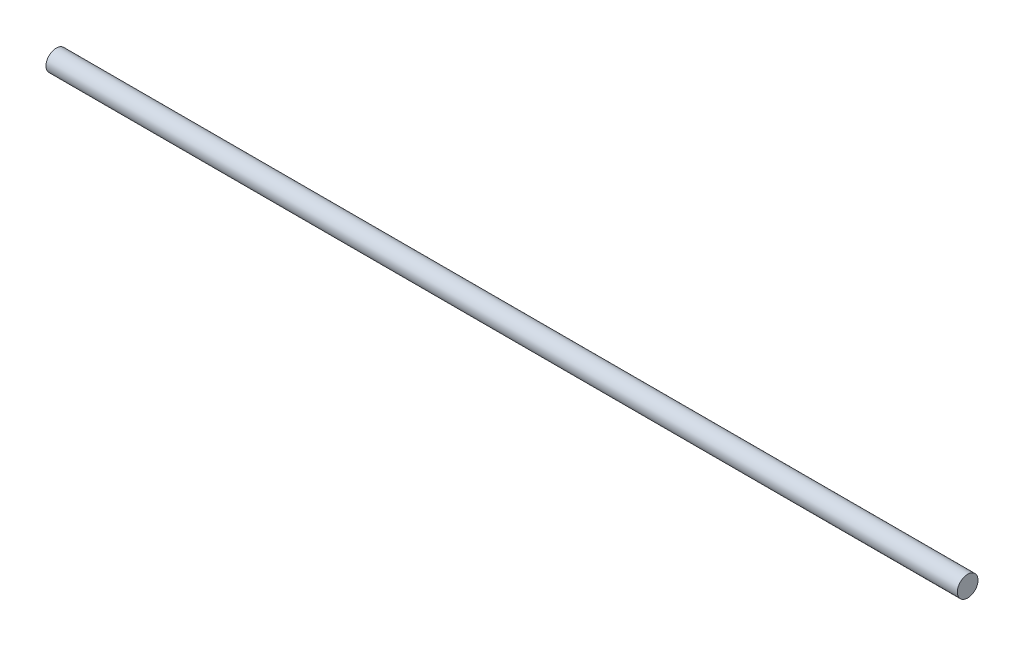
SolidWorks part; units mm, degrees
ref_plane "Front Plane" through (0, 0, 0) normal (0, 0, 1) x (1, 0, 0)
ref_plane "Top Plane" through (0, 0, 0) normal (0, 1, 0) x (1, 0, 0)
ref_plane "Right Plane" through (0, 0, 0) normal (1, 0, 0) x (0, 0, -1)
sketch "Sketch1" plane through (0, 0, 0) normal (1, 0, 0) x (0, 0, -1)
  circle A0 centre (0, 0) radius 1.505
  dimension "D1" = 3.0099
extrude "Boss-Extrude1" add sketch "Sketch1" along normal mid plane 132.842
